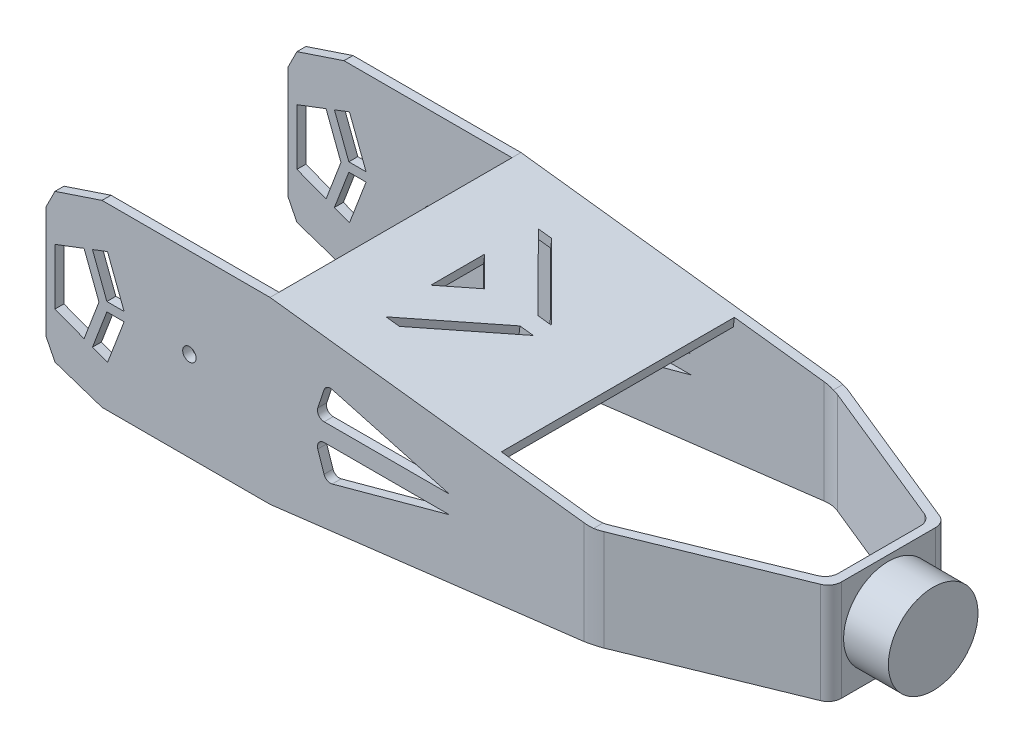
SolidWorks part; units mm, degrees
ref_plane "Front" through (0, 0, 0) normal (0, 0, 1) x (1, 0, 0)
ref_plane "Top" through (0, 0, 0) normal (0, 1, 0) x (1, 0, 0)
ref_plane "Right" through (0, 0, 0) normal (1, 0, 0) x (0, 0, -1)
sketch "草图1" plane through (0, 0, 0) normal (0, 1, 0) x (1, 0, 0)
  line L0 (-80, 0) -> (80, 0) construction
  line L1 (42, -28) -> (-80, -28)
  line L2 (80, -12.5) -> (80, 12.5)
  line L3 (42, 28) -> (-80, 28)
  line L4 (-80, -28) -> (-80, 28)
  line L5 (42, 28) -> (80, 12.5)
  line L6 (80, -12.5) -> (42, -28)
  point P5 (42, 28)
  point P6 (80, 12.5)
  point P11 (42, -28)
  point P12 (80, -12.5)
  dimension "D1" = 160
  dimension "D2" = 56
  dimension "D3" = 122
  dimension "D4" = 12.5
  dimension "D5" = 15.5
extrude "凸台-拉伸1" add sketch "草图1" along normal mid plane 40
shell "抽壳1" thickness 2 removed face at (-80, 0, 0) removed face at (14, -20, 0) removed face at (14, 20, 0)
sketch "草图2" plane through (0, 0, 28) normal (0, 0, 1) x (1, 0, 0)
  line L0 (-80, 0) -> (79.3241, 0) construction
  line L1 (-80, 20) -> (-80, -20) construction
  line L2 (-80, 12.5) -> (-78, 16.5)
  line L3 (-78, 16.5) -> (-67.5, 20)
  line L4 (-80, 20) -> (42, 20) construction
  line L5 (-67.5, 20) -> (-80, 20)
  line L6 (-80, 20) -> (-80, 12.5)
  line L7 (-80, -12.5) -> (-78, -16.5)
  line L8 (-78, -16.5) -> (-67.5, -20)
  line L9 (-67.5, -20) -> (-80, -20)
  line L10 (-80, -20) -> (-80, -12.5)
  line L11 (-30, 20) -> (42, 11.25)
  line L12 (42, 20) -> (42, -20) construction
  line L13 (42, 11.25) -> (80, 11.25)
  line L14 (80, 20) -> (80, -20) construction
  line L16 (-30, 20) -> (80, 20)
  line L17 (80, 20) -> (80, 11.25)
  line L18 (42, -11.25) -> (80, -11.25)
  line L19 (80, -20) -> (80, -11.25)
  line L20 (-30, -20) -> (80, -20)
  line L21 (-30, -20) -> (42, -11.25)
  point P21 (0, 0)
  dimension "D1" = 12.5
  dimension "D2" = 2
  dimension "D3" = 4
  dimension "D4" = 12.5
  dimension "D5" = 50
  dimension "D6" = 11.25
extrude "切除-拉伸1" cut sketch "草图2" against normal through all
fillet "圆角1" radius 10 4 edges at (41.6078, 0, 26) (42, 0, -28) (41.6078, 0, -26) (42, 0, 28)
fillet "圆角2" radius 3 4 edges at (78, 0, 11.1558) (78, 0, -11.1558) (80, 0, 12.5) (80, 0, -12.5)
sketch "草图3" plane through (1.9586, 16.1161, 0) normal (0.1206, 0.9927, 0) x (0.9927, -0.1206, 0)
  line L0 (-32.1937, 26) -> (37.9655, 26) construction
  line L1 (17.8063, 26) -> (-32.1937, 26)
  line L2 (17.8063, 26) -> (17.8063, -26)
  line L3 (17.8063, -26) -> (-32.1937, -26)
  line L4 (-32.1937, 26) -> (-32.1937, -26)
  line L5 (17.8063, 26) -> (-32.1937, -26) construction
  line L6 (17.8063, -26) -> (-32.1937, 26) construction
  line L7 (37.9655, -26) -> (-32.1937, -26) construction
  line L8 (-32.1937, 28) -> (-32.1937, 26) construction
  point P0 (-26.624, 26)
  point P7 (0, 0)
  point P12 (-32.1937, 27)
  dimension "D1" = 50
extrude "凸台-拉伸2" add sketch "草图3" against normal blind 2
sketch "草图4" plane through (80, 0, 0) normal (1, 0, 0) x (0, 0, -1)
  circle A0 centre (0, 0) radius 10
  dimension "D1" = 20
extrude "凸台-拉伸3" add sketch "草图4" along normal blind 10
sketch "草图5" plane through (0, 0, 28) normal (0, 0, 1) x (1, 0, 0)
  line L0 (-80, 12.5) -> (-80, -12.5) construction
  circle A0 centre (-48, 0) radius 1.5
  dimension "D1" = 32
  dimension "D2" = 3
extrude "切除-拉伸2" cut sketch "草图5" against normal through all
sketch "草图6" plane through (1.9586, 16.1161, 0) normal (0.1206, 0.9927, 0) x (0.9927, -0.1206, 0)
  line L0 (-32.1937, 0) -> (17.8063, 0) construction
  line L1 (-32.1937, 26) -> (-32.1937, -26) construction
  line L2 (17.8063, -26) -> (17.8063, 26) construction
  line L3 (-18.1937, -6) -> (-18.1937, 6)
  line L4 (-18.1937, 6) -> (-12.1937, 0)
  line L5 (-2.1937, 2) -> (-17.1937, 17)
  line L6 (-17.1937, 17) -> (-14.1937, 17)
  line L7 (-14.1937, 17) -> (0.8063, 2)
  line L8 (0.8063, 2) -> (-2.1937, 2)
  line L9 (-14.1937, -17) -> (0.8063, -2)
  line L10 (-17.1937, -17) -> (-14.1937, -17)
  line L11 (-2.1937, -2) -> (-17.1937, -17)
  line L12 (0.8063, -2) -> (-2.1937, -2)
  line L13 (-18.1937, -6) -> (-12.1937, 0)
  point P18 (-18.1937, 0)
  dimension "D1" = 14
  dimension "D2" = 6
  dimension "D3" = 6
  dimension "D4" = 17
  dimension "D5" = 1
  dimension "D6" = 2
  dimension "D7" = 3
extrude "切除-拉伸3" cut sketch "草图6" against normal through all
sketch "草图7" plane through (0, 0, 28) normal (0, 0, 1) x (1, 0, 0)
  line L0 (-80, 0) -> (40.039, 0) construction
  line L1 (-80, 12.5) -> (-80, -12.5) construction
  line L2 (40.039, -11.4883) -> (40.039, 11.4883) construction
  line L3 (-17.9189, 2) -> (10, 2)
  line L4 (-19.3419, 3.9743) -> (-17.9487, 8.1538)
  line L5 (-16.131, 9.1266) -> (10, 2)
  line L6 (-19.3419, -3.9743) -> (-17.9487, -8.1538)
  line L7 (-17.9189, -2) -> (10, -2)
  line L8 (-16.131, -9.1266) -> (10, -2)
  arc A0 (-17.9189, 2) -> (-19.3419, 3.9743) centre (-17.9189, 3.5) cw
  arc A1 (-16.131, 9.1266) -> (-17.9487, 8.1538) centre (-16.5257, 7.6795) ccw
  arc A2 (-17.9189, -2) -> (-19.3419, -3.9743) centre (-17.9189, -3.5) ccw
  arc A3 (-16.131, -9.1266) -> (-17.9487, -8.1538) centre (-16.5257, -7.6795) cw
  point P12 (-20, 2)
  point P15 (-17.5, 9.5)
  dimension "D6" = 1.5
  dimension "D1" = 2
  dimension "D2" = 30
  dimension "D3" = 10
  dimension "D4" = 7.5
  dimension "D5" = 2.5
extrude "切除-拉伸4" cut sketch "草图7" against normal up to next
mirror "镜向1" about plane through (0, 0, 0) normal (0, 0, 1) of "切除-拉伸4"
sketch "草图8" plane through (0, 0, 28) normal (0, 0, 1) x (1, 0, 0)
  line L0 (-80, 0) -> (40.039, 0) construction
  line L1 (-80, 12.5) -> (-80, -12.5) construction
  line L2 (40.039, -11.4883) -> (40.039, 11.4883) construction
  line L3 (-78, -6.25) -> (-78, 6.25)
  line L4 (-78, 6.25) -> (-71.5, 8.7273)
  line L5 (-71.5, 8.7273) -> (-68.1738, 0)
  line L6 (-66.4146, 1) -> (-69.6311, 9.4396)
  line L7 (-69.6311, 9.4396) -> (-66.2722, 10.7197)
  line L8 (-66.2722, 10.7197) -> (-62.5678, 1)
  line L9 (-62.5678, 1) -> (-66.4146, 1)
  line L10 (-66.2722, -10.7197) -> (-62.5678, -1)
  line L11 (-69.6311, -9.4396) -> (-66.2722, -10.7197)
  line L12 (-66.4146, -1) -> (-69.6311, -9.4396)
  line L13 (-62.5678, -1) -> (-66.4146, -1)
  line L14 (-71.5, -8.7273) -> (-68.1738, 0)
  line L15 (-78, -6.25) -> (-71.5, -8.7273)
  point P20 (-78, 0)
  dimension "D1" = 6.25
  dimension "D2" = 2
  dimension "D3" = 8.5
  dimension "D4" = 8.7273
  dimension "D5" = 2
  dimension "D6" = 1
extrude "切除-拉伸5" cut sketch "草图8" against normal through all
